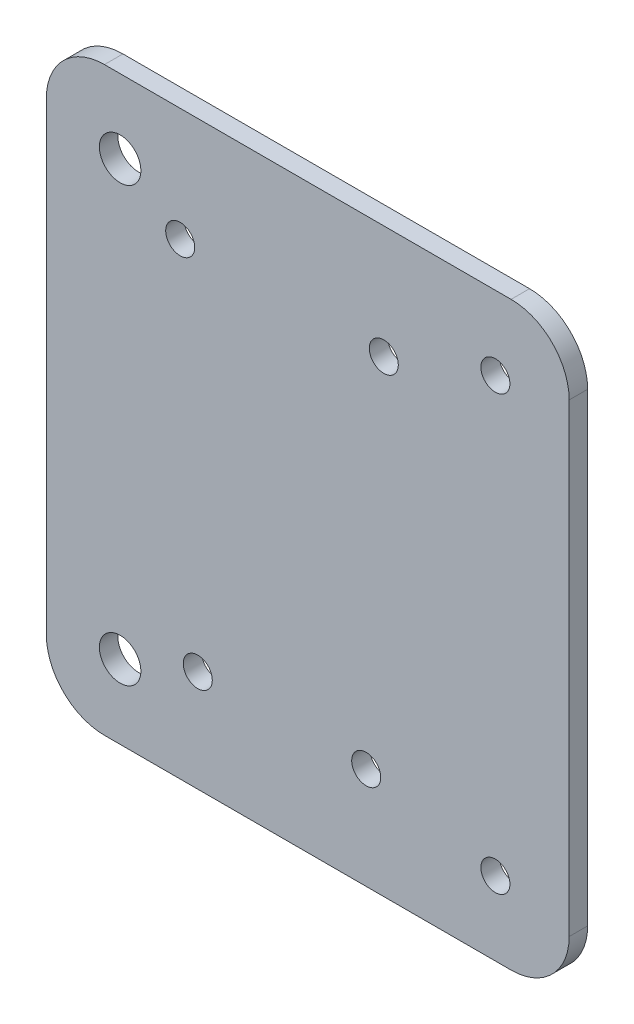
SolidWorks part; units mm, degrees
ref_plane "Front Plane" through (0, 0, 0) normal (0, 0, 1) x (1, 0, 0)
ref_plane "Top Plane" through (0, 0, 0) normal (0, 1, 0) x (1, 0, 0)
ref_plane "Right Plane" through (0, 0, 0) normal (1, 0, 0) x (0, 0, -1)
sketch "Sketch1" plane through (0, 0, 0) normal (0, 0, 1) x (1, 0, 0)
  line L1 (-45, -55) -> (45, -55)
  line L2 (-45, -55) -> (-45, 45)
  line L3 (-45, 45) -> (45, 45)
  line L4 (45, -55) -> (45, 45)
  circle A5 centre (32.3, -42.3) radius 2.5
  circle A6 centre (-32.3, -42.3) radius 3.57
  circle A9 centre (-32.3, 32.3) radius 3.57
  circle A11 centre (32.3, 32.3) radius 2.5
extrude "Boss-Extrude1" add sketch "Sketch1" against normal blind 3.18
fillet "Fillet1" radius 10 4 edges at (45, -55, -1.59) (-45, -55, -1.59) (-45, 45, -1.59) (45, 45, -1.59)
sketch "Sketch2" plane through (0, 0, 0) normal (0, 0, 1) x (1, 0, 0)
  circle A0 centre (-18.9354, -37.5) radius 2.5
  circle A1 centre (10.0646, -37.5) radius 2.5
  circle A2 centre (-21.9586, 25.5078) radius 2.5
  circle A3 centre (13.0877, 25.5078) radius 2.5
  dimension "D1" = 5
extrude "Cut-Extrude1" cut sketch "Sketch2" against normal blind 10
